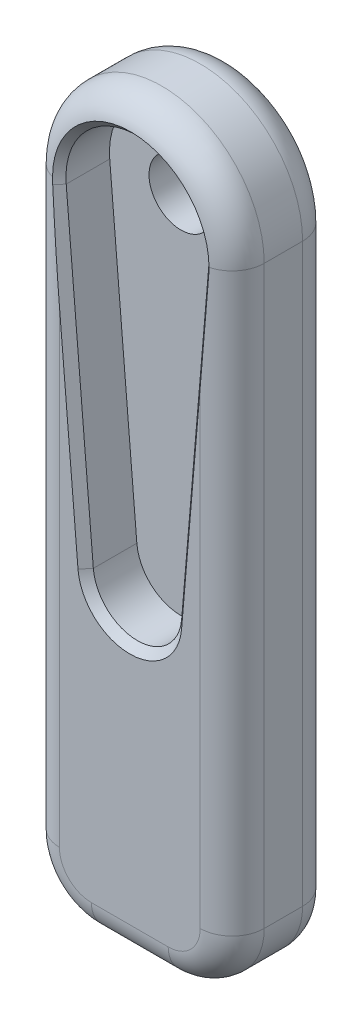
SolidWorks part; units mm, degrees
material "Nylon 101"
ref_plane "Front" through (0, 0, 0) normal (0, 0, 1) x (1, 0, 0)
ref_plane "Top" through (0, 0, 0) normal (0, 1, 0) x (1, 0, 0)
ref_plane "Right" through (0, 0, 0) normal (1, 0, 0) x (0, 0, -1)
sketch "Sketch1" plane through (0, 0, 0) normal (0, 0, 1) x (1, 0, 0)
  line L0 (-3.338, -0.2835) -> (-1.9928, -16.1193) construction
  line L1 (1.9928, -16.1193) -> (3.338, -0.2835) construction
  line L2 (0, 0) -> (0, -31.75) construction
  line L3 (5.08, -28.575) -> (5.08, 0)
  line L4 (-5.08, -28.575) -> (-5.08, 0)
  line L5 (-3.5357, -0.3003) -> (-2.1905, -16.1361)
  line L6 (2.1905, -16.1361) -> (3.5357, -0.3003)
  line L7 (-1.905, -31.75) -> (1.905, -31.75)
  arc A0 (0, 1.15) -> (0, -1.15) centre (0, 0) ccw construction
  arc A1 (3.338, -0.2835) -> (-3.338, -0.2835) centre (0, 0) ccw construction
  arc A2 (-1.9928, -16.1193) -> (0, -17.95) centre (0, -15.95) ccw construction
  arc A3 (0, -17.95) -> (1.9928, -16.1193) centre (0, -15.95) ccw construction
  arc A4 (0, -1.15) -> (0, 1.15) centre (0, 0) ccw construction
  arc A5 (5.08, 0) -> (-5.08, 0) centre (0, 0) ccw
  arc A7 (-2.1905, -16.1361) -> (0, -18.1484) centre (0, -15.95) ccw
  arc A8 (0, -18.1484) -> (2.1905, -16.1361) centre (0, -15.95) ccw
  arc A9 (3.5357, -0.3003) -> (-3.5357, -0.3003) centre (0, 0) ccw
  circle A10 centre (0, 0) radius 1.5875
  arc A11 (-1.905, -31.75) -> (-5.08, -28.575) centre (-1.905, -28.575) cw
  arc A12 (5.08, -28.575) -> (1.905, -31.75) centre (1.905, -28.575) cw
  point P26 (-5.08, -31.75)
  point P29 (5.08, -31.75)
  dimension "D1" = 3.35
  dimension "D3" = 5.08
  dimension "D4" = 3.175
  dimension "D7" = 3.175
  dimension "D2" = 10.16
  dimension "D5" = 31.75
  dimension "D6" = 0.1984
extrude "Boss-Extrude1" add sketch "Sketch1" along normal blind 2.54 contours L4 L7 L3 A5 A9 L6 A8 A7 L5 region at (3.8799, -30.5499, 0)
extrude "Boss-Extrude2" add sketch "Sketch1<3>" against normal blind 2.54 contours L6 A9 L5 A7 A8 A4 A0 | L4 L7 L3 A5 A9 L6 A8 A7 L5 region at (3.8799, -30.5499, 0) region at (0, -6.9505, 0)
sketch "Sketch1<3>" plane through (0, 0, 0) normal (0, 0, 1) x (1, 0, 0) same geometry as "Sketch1"
chamfer "Chamfer1" distance 0.381 angle 45 4 edges at (2.8631, -8.2182, 2.54) (0, 3.5484, 2.54) (0, -18.1484, 2.54) (-2.8631, -8.2182, 2.54)
fillet "Fillet1" radius 1.5875 12 edges at (4.1501, -30.8201, 2.54) (-4.1501, -30.8201, 2.54) (-5.08, -14.2875, 2.54) (0, 5.08, 2.54) (4.1501, -30.8201, -2.54) (-4.1501, -30.8201, -2.54) (-5.08, -14.2875, -2.54) (0, 5.08, -2.54) (0, -31.75, 2.54) (5.08, -14.2875, 2.54) (0, -31.75, -2.54) (5.08, -14.2875, -2.54)
